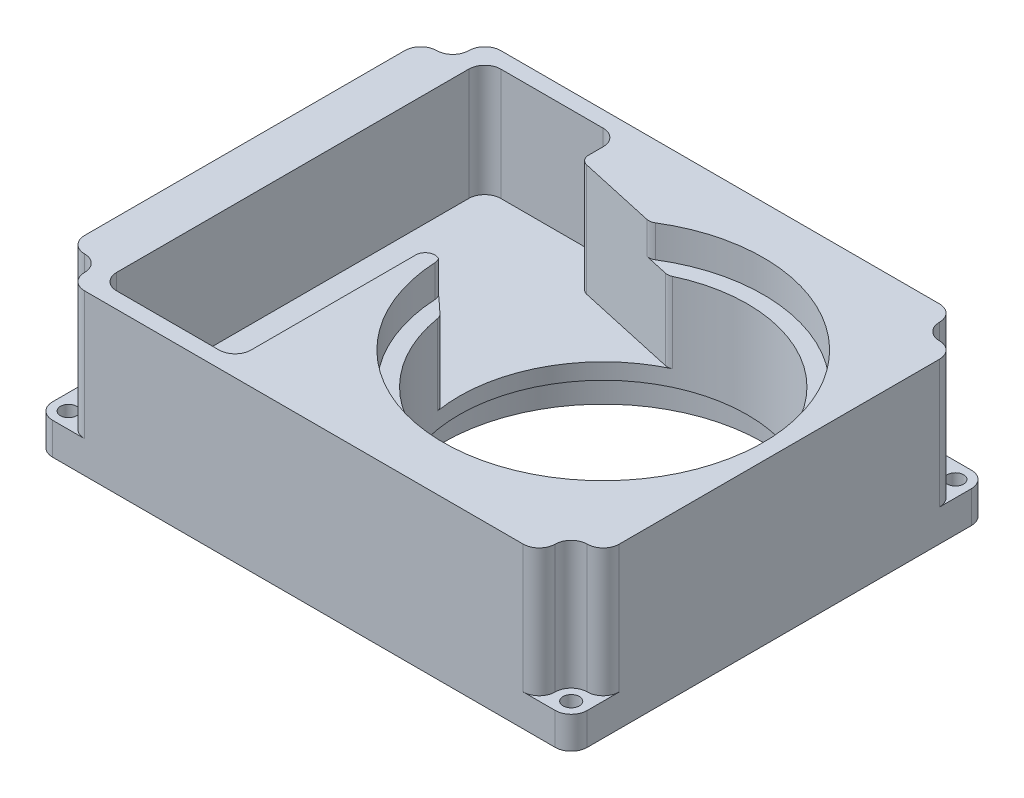
SolidWorks part; units mm, degrees
ref_plane "Front Plane" through (0, 0, 0) normal (0, 0, 1) x (1, 0, 0)
ref_plane "Top Plane" through (0, 0, 0) normal (0, 1, 0) x (1, 0, 0)
ref_plane "Right Plane" through (0, 0, 0) normal (1, 0, 0) x (0, 0, -1)
sketch "Sketch1" plane through (0, 0, 0) normal (0, 1, 0) x (1, 0, 0)
  line L1 (-83.5, -65) -> (83.5, -65)
  line L2 (-83.5, -65) -> (-83.5, 65)
  line L3 (-83.5, 65) -> (83.5, 65)
  line L4 (83.5, -65) -> (83.5, 65)
  line L5 (-83.5, -65) -> (83.5, 65) construction
  line L6 (-83.5, 65) -> (83.5, -65) construction
  point P0 (0, 0)
  dimension "D1" = 167
  dimension "D2" = 130
extrude "Boss-Extrude1" add sketch "Sketch1" along normal blind 50
sketch "Sketch2" plane through (0, 50, 0) normal (0, 1, 0) x (1, 0, 0)
  line L0 (83.5, -65) -> (83.5, 65) construction
  circle A0 centre (28.5, 0) radius 45
  dimension "D1" = 90
  dimension "D2" = 55
extrude "Cut-Extrude1" cut sketch "Sketch2" against normal through all
sketch "Sketch3" plane through (0, 50, 0) normal (0, 1, 0) x (1, 0, 0)
  circle A0 centre (28.5, 0) radius 50
  dimension "D1" = 100
extrude "Cut-Extrude2" cut sketch "Sketch3" against normal blind 10
sketch "Sketch4" plane through (0, 0, 0) normal (0, -1, 0) x (1, 0, 0)
  circle A0 centre (28.5, 0) radius 50
  circle A1 centre (28.5, 0) radius 45 construction
  dimension "D1" = 100
extrude "Cut-Extrude3" cut sketch "Sketch4" against normal blind 10
sketch "Sketch7" plane through (0, 50, 0) normal (0, 1, 0) x (1, 0, 0)
  line L1 (-68.5, -60) -> (-26.5, -60)
  line L2 (-68.5, -60) -> (-68.5, 60)
  line L3 (-68.5, 60) -> (-26.5, 60)
  line L4 (-26.5, -60) -> (-26.5, 60)
  line L5 (-68.5, -60) -> (-26.5, 60) construction
  line L6 (-68.5, 60) -> (-26.5, -60) construction
  circle A0 centre (28.5, 0) radius 45 construction
  point P0 (-47.5, 0)
  dimension "D3" = 76
  dimension "D1" = 42
  dimension "D2" = 120
  dimension "D4" = 0
extrude "Cut-Extrude5" cut sketch "Sketch7" against normal blind 35
sketch "Sketch10" plane through (0, 50, 0) normal (0, 1, 0) x (1, 0, 0)
  line L0 (-44.7995, 52.0654) -> (36.0615, 34.1734)
  line L1 (-56.0051, 30.7002) -> (4.6857, -25.6491)
  line L2 (-47.5, -940) -> (-47.5, 49060) construction
  line L3 (-26.5, 60) -> (-68.5, 60) construction
  arc A0 (4.6857, -25.6491) -> (36.0615, 34.1734) centre (28.5, 0) ccw
  arc A1 (-44.7995, 52.0654) -> (-56.0051, 30.7002) centre (-47.5, 39.8606) ccw
  point P14 (-47.5, 60)
  dimension "D1" = 70
  dimension "D3" = 25
extrude "Cut-Extrude7" cut sketch "Sketch10" against normal blind 35
sketch "Sketch11" plane through (0, 50, 0) normal (0, 1, 0) x (1, 0, 0)
  line L1 (-83.5, 65) -> (-73.5, 65)
  line L2 (-83.5, 65) -> (-83.5, 55)
  line L3 (-83.5, 55) -> (-73.5, 55)
  line L4 (-73.5, 65) -> (-73.5, 55)
  line L5 (83.5, 65) -> (73.5, 65)
  line L6 (83.5, 65) -> (83.5, 55)
  line L7 (83.5, 55) -> (73.5, 55)
  line L8 (73.5, 65) -> (73.5, 55)
  line L9 (83.5, -65) -> (73.5, -65)
  line L10 (83.5, -65) -> (83.5, -55)
  line L11 (83.5, -55) -> (73.5, -55)
  line L12 (73.5, -65) -> (73.5, -55)
  line L13 (-83.5, -65) -> (-73.5, -65)
  line L14 (-83.5, -65) -> (-83.5, -55)
  line L15 (-83.5, -55) -> (-73.5, -55)
  line L16 (-73.5, -65) -> (-73.5, -55)
  dimension "D1" = 10
  dimension "D2" = 10
  dimension "D3" = 10
  dimension "D4" = 10
  dimension "D5" = 10
  dimension "D6" = 10
  dimension "D7" = 10
extrude "Cut-Extrude8" cut sketch "Sketch11" against normal blind 40
sketch "Sketch12" plane through (0, 10, 0) normal (0, 1, 0) x (1, 0, 0)
  line L0 (-83.5, 65) -> (-73.5, 55) construction
  line L1 (83.5, 65) -> (73.5, 55) construction
  line L2 (-73.5, -55) -> (-83.5, -65) construction
  line L4 (73.5, -55) -> (83.5, -65) construction
  circle A0 centre (-78.5, 60) radius 2.55
  circle A1 centre (78.5, 60) radius 2.55
  circle A2 centre (78.5, -60) radius 2.55
  circle A3 centre (-78.5, -60) radius 2.55
  dimension "D1" = 5.1
  dimension "D2" = 5.1
  dimension "D3" = 5.1
  dimension "D4" = 5.1
extrude "Cut-Extrude9" cut sketch "Sketch12" against normal blind 40
fillet "Fillet1" radius 5 12 edges at (-68.5, 32.5, 60) (-26.5, 32.5, 60) (-26.5, 32.5, -60) (-68.5, 32.5, -60) (73.5, 30, -55) (73.5, 30, 55) (-73.5, 30, 55) (-73.5, 30, -55) (83.5, 5, -65) (-83.5, 5, -65) (83.5, 5, 65) (-83.5, 5, 65)
fillet "Fillet2" radius 5 8 edges at (73.5, 30, -65) (83.5, 30, -55) (83.5, 30, 55) (-73.5, 30, 65) (-83.5, 30, 55) (-73.5, 30, -65) (-83.5, 30, -55) (73.5, 30, 65)
fillet "Fillet3" radius 3 6 edges at (-21.4817, 45, 1.3536) (-16.042, 27.5, 6.4042) (-26.5, 32.5, -3.3057) (8.4452, 27.5, -40.284) (1.1976, 45, -41.8877) (-26.5, 32.5, -48.0163)
